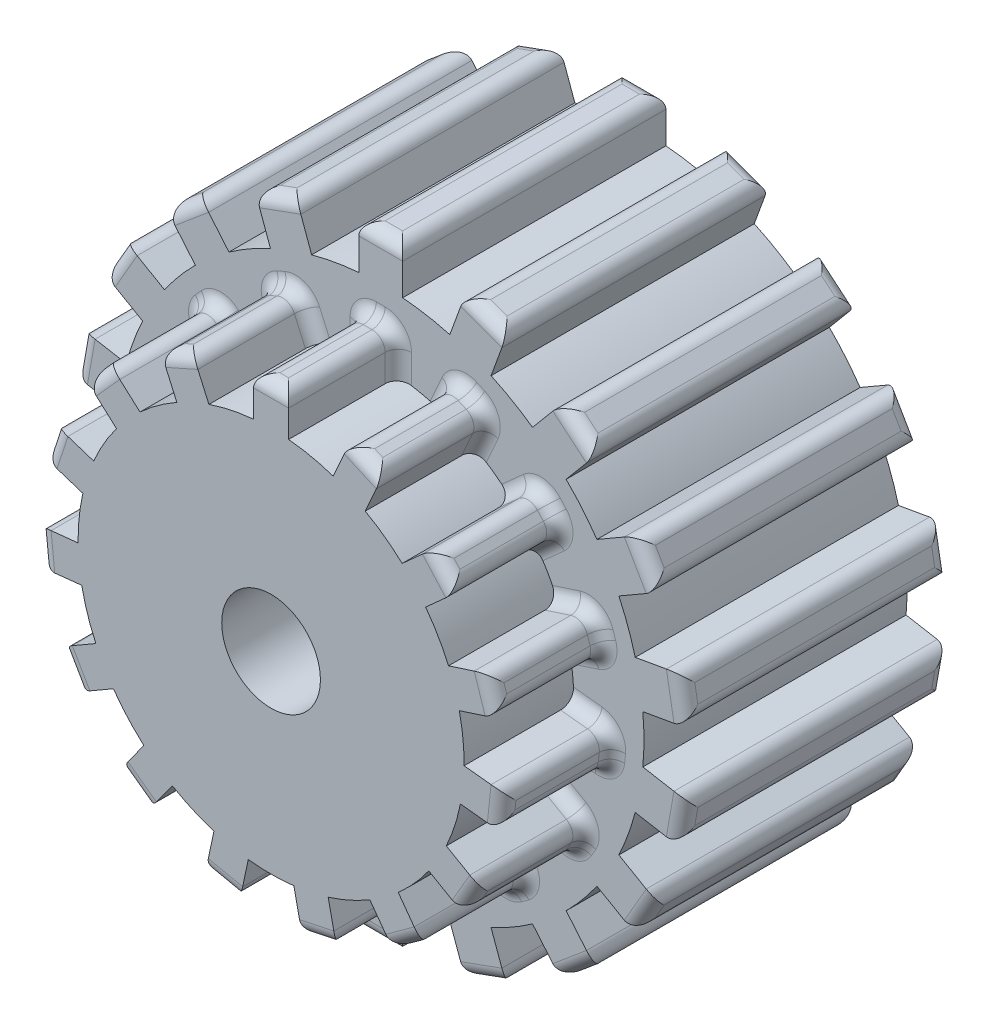
SolidWorks part; units mm, degrees
ref_plane "Front Plane" through (0, 0, 0) normal (0, 0, 1) x (1, 0, 0)
ref_plane "Top Plane" through (0, 0, 0) normal (0, 1, 0) x (1, 0, 0)
ref_plane "Right Plane" through (0, 0, 0) normal (1, 0, 0) x (0, 0, -1)
sketch "Sketch2" plane through (0, 0, 0) normal (0, 0, 1) x (1, 0, 0)
  circle A0 centre (0, 0) radius 60
extrude "Boss-Extrude1" add sketch "Sketch2" along normal blind 60
sketch "Sketch3" plane through (0, 0, 60) normal (0, 0, 1) x (1, 0, 0)
  line L0 (0, 60) -> (0, 70) construction
  line L1 (5, 70) -> (-5, 70)
  line L2 (-5, 70) -> (-5, 59.5215)
  line L3 (-5, 59.5215) -> (5, 59.5215)
  line L4 (5, 59.5215) -> (5, 70)
  circle A0 centre (0, 0) radius 60 construction
  point P9 (0, 70)
extrude "Boss-Extrude2" add sketch "Sketch3" against normal blind 60
fillet "Fillet2" radius 3 4 edges at (-5, 70, 30) (0, 70, 0) (5, 70, 30) (0, 70, 60)
pattern_circular "CirPattern1" count 18 over 360 about axis through (0, 0, 60) along (0, 0, -1) of "Fillet2", "Boss-Extrude2" reverse direction yes
sketch "Sketch4" plane through (0, 0, 60) normal (0, 0, 1) x (1, 0, 0)
  circle A0 centre (0, 0) radius 10
extrude "Cut-Extrude1" cut sketch "Sketch4" against normal blind 60
sketch "Sketch5" plane through (0, 0, 60) normal (0, 0, 1) x (1, 0, 0)
  circle A0 centre (0, 0) radius 44
extrude "Boss-Extrude3" add sketch "Sketch5" along normal blind 25
sketch "Sketch6" plane through (0, 0, 85) normal (0, 0, 1) x (1, 0, 0)
  line L0 (0, 44) -> (0, 53) construction
  line L1 (4, 53) -> (-4, 53)
  line L2 (-4, 53) -> (-4, 42.9556)
  line L3 (-4, 42.9556) -> (4, 42.9556)
  line L4 (4, 42.9556) -> (4, 53)
  circle A0 centre (0, 0) radius 44 construction
  circle A1 centre (0, 0) radius 44 construction
  point P10 (0, 53)
extrude "Boss-Extrude4" add sketch "Sketch6" against normal blind 25
sketch "Sketch7" plane through (0, 0, 0) normal (0, 0, -1) x (-1, 0, 0)
  circle A0 centre (0, 0) radius 10
extrude "Cut-Extrude2" cut sketch "Sketch7" against normal blind 90
fillet "Fillet3" radius 3 6 edges at (-4, 48.4089, 60) (4, 48.4089, 60) (-4, 53, 72.5) (0, 53, 60) (4, 53, 72.5) (0, 53, 85)
pattern_circular "CirPattern2" count 15 over 360 about axis through (0, 0, 85) along (0, 0, -1) of "Boss-Extrude4", "Fillet3" reverse direction yes
sketch "Sketch8" plane through (0, 0, 0) normal (0, 0, -1) x (-1, 0, 0)
  circle A0 centre (0, 0) radius 11.25
extrude "Cut-Extrude3" cut sketch "Sketch8" against normal up to surface (85 mm away) up to face at (0, 0, 85)
scale "Scale1" bodies to scale 119 scale about centroid uniform scaling yes scale factor 0.2
